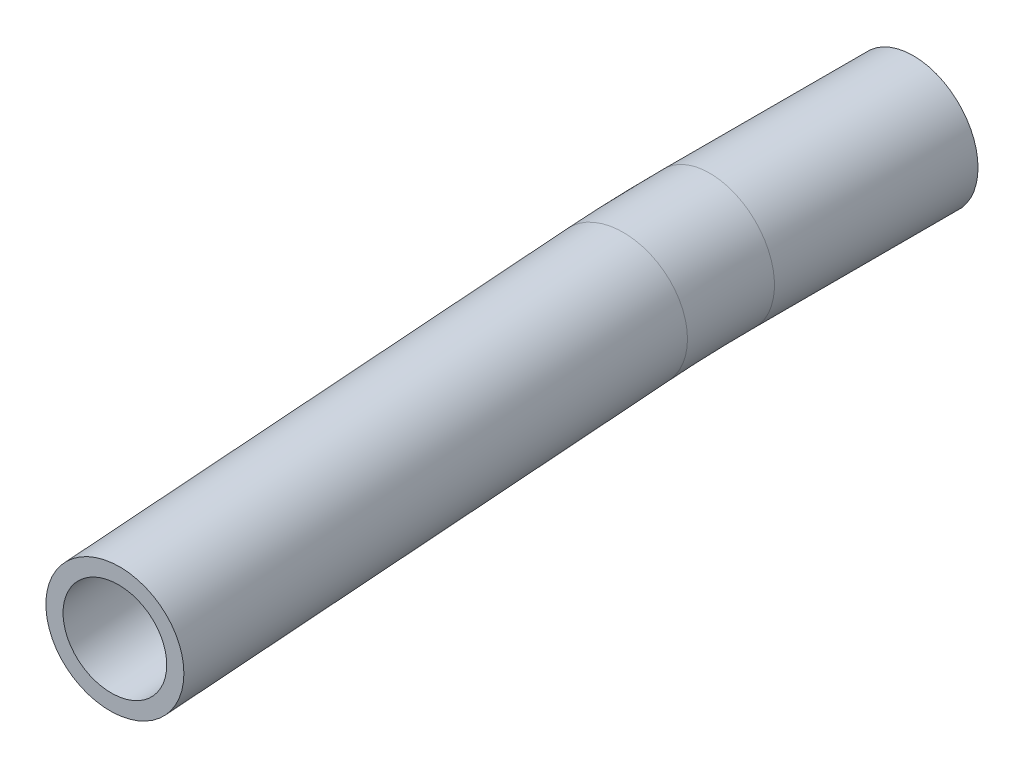
SolidWorks part; units mm, degrees
material "ПК/АБС"
ref_plane "Спереди" through (0, 0, 0) normal (0, 0, 1) x (1, 0, 0)
ref_plane "Сверху" through (0, 0, 0) normal (0, 1, 0) x (1, 0, 0)
ref_plane "Справа" through (0, 0, 0) normal (1, 0, 0) x (0, 0, -1)
sketch "Эскиз1" plane through (0, 0, 0) normal (0, 0, 1) x (1, 0, 0)
  circle A0 centre (0, 0) radius 3.58
  circle A1 centre (0, 0) radius 4.765
  dimension "D1" = 7.16
  dimension "D2" = 9.53
sketch3d "Трехмерный эскиз1"
  line L0 (0, 0, 0) -> (0, 0, 15)
  line L1 (0.2436, 0, 21.9756) -> (3.0339, 0, 61.8782)
  arc A0 (0, 0, 15) -> (0.2436, 0, 21.9756) centre (100, 0, 15) ccw
  point P3 (100, 100, 15)
  dimension "D1" = 100
  dimension "D2" = 15
  dimension "D3" = 40
  dimension "D4" = 4
sweep "По траектории1" add profiles "Эскиз1" path "Трехмерный эскиз1"
ref_axis "Ось1" through (0.1973, 0, 21.3141) along (0.0698, 0, 0.9976)
ref_axis "Ось2" through (0, 0, 15) along (0, 0, -1)
ref_plane "Плоскость1" through (0, 0, 0) normal (0, 1, 0) x (-1, 0, 0)
